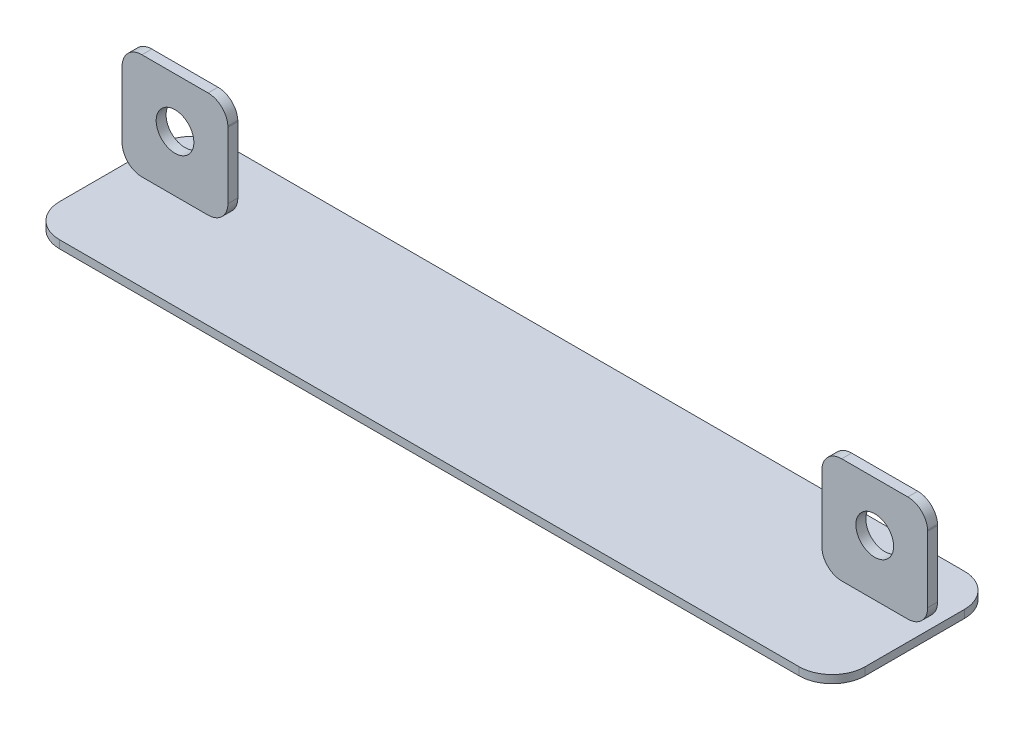
SolidWorks part; units mm, degrees
ref_plane "Front Plane" through (0, 0, 0) normal (0, 0, 1) x (1, 0, 0)
ref_plane "Top Plane" through (0, 0, 0) normal (0, 1, 0) x (1, 0, 0)
ref_plane "Right Plane" through (0, 0, 0) normal (1, 0, 0) x (0, 0, -1)
sketch "Sketch3" plane through (0, 0, 0) normal (0, 0, 1) x (1, 0, 0)
  line L6 (-7.9975, -43.2281) -> (-8, -43.4)
  line L7 (-8, -43.4) -> (-8, -53.4)
  line L8 (-5, -56.4) -> (5, -56.4)
  line L9 (8, -53.4) -> (8, -43.4)
  line L10 (8, -43.4) -> (7.9975, -43.2281)
  line L11 (5, -40.4) -> (-5, -40.4)
  line L12 (-7.9975, -43.2281) -> (-8, -43.4)
  line L13 (-8, -43.4) -> (-8, -53.4)
  line L14 (-5, -56.4) -> (5, -56.4)
  line L15 (8, -53.4) -> (8, -43.4)
  line L16 (8, -43.4) -> (7.9975, -43.2281)
  line L17 (5, -40.4) -> (-5, -40.4)
  line L18 (110.8, -40.4) -> (100.8, -40.4)
  line L19 (97.8025, -43.2281) -> (97.8, -43.4)
  line L20 (97.8, -43.4) -> (97.8, -53.4)
  line L21 (100.8, -56.4) -> (110.8, -56.4)
  line L22 (113.8, -53.4) -> (113.8, -43.4)
  line L23 (113.8, -43.4) -> (113.7975, -43.2281)
  line L24 (110.8, -40.4) -> (100.8, -40.4)
  line L25 (97.8025, -43.2281) -> (97.8, -43.4)
  line L26 (97.8, -43.4) -> (97.8, -53.4)
  line L27 (100.8, -56.4) -> (110.8, -56.4)
  line L28 (113.8, -53.4) -> (113.8, -43.4)
  line L29 (113.8, -43.4) -> (113.7975, -43.2281)
  circle A0 centre (0, -47.9524) radius 2.85 construction
  circle A1 centre (0, -47.9524) radius 2.85
  arc A2 (-5, -40.4) -> (-7.9975, -43.2281) centre (-5.0013, -43.4012) ccw
  arc A3 (-8, -53.4) -> (-5, -56.4) centre (-5, -53.4) ccw
  arc A4 (5, -56.4) -> (8, -53.4) centre (5, -53.4) ccw
  arc A5 (7.9975, -43.2281) -> (5, -40.4) centre (5.0013, -43.4012) ccw
  arc A6 (-5, -40.4) -> (-7.9975, -43.2281) centre (-5.0013, -43.4012) ccw
  arc A7 (-8, -53.4) -> (-5, -56.4) centre (-5, -53.4) ccw
  arc A8 (5, -56.4) -> (8, -53.4) centre (5, -53.4) ccw
  arc A9 (7.9975, -43.2281) -> (5, -40.4) centre (5.0013, -43.4012) ccw
  circle A10 centre (105.8, -47.9524) radius 2.85 construction
  circle A11 centre (105.8, -47.9524) radius 2.85
  arc A12 (100.8, -40.4) -> (97.8025, -43.2281) centre (100.7987, -43.4012) ccw
  arc A13 (97.8, -53.4) -> (100.8, -56.4) centre (100.8, -53.4) ccw
  arc A14 (110.8, -56.4) -> (113.8, -53.4) centre (110.8, -53.4) ccw
  arc A15 (113.7975, -43.2281) -> (110.8, -40.4) centre (110.8013, -43.4012) ccw
  arc A16 (100.8, -40.4) -> (97.8025, -43.2281) centre (100.7987, -43.4012) ccw
  arc A17 (97.8, -53.4) -> (100.8, -56.4) centre (100.8, -53.4) ccw
  arc A18 (110.8, -56.4) -> (113.8, -53.4) centre (110.8, -53.4) ccw
  arc A19 (113.7975, -43.2281) -> (110.8, -40.4) centre (110.8013, -43.4012) ccw
  dimension "D1" = 0
  dimension "D2" = 0
extrude "Boss-Extrude3" add sketch "Sketch3" along normal up to surface (1.5 mm away)
sketch "Sketch2" plane through (0, -56.4, 0) normal (0, -1, 0) x (1, 0, 0)
  line L0 (-8, -78.8637) -> (-8, 0) construction
  line L1 (-8, -9.0521) -> (113.8, -9.0521)
  line L2 (-8, -9.0521) -> (-8, 15.9479)
  line L3 (-8, 15.9479) -> (113.8, 15.9479)
  line L4 (113.8, -9.0521) -> (113.8, 15.9479)
  line L5 (113.8, 0) -> (113.8, -78.8637) construction
  line L6 (-5, 15.9479) -> (5, 15.9479) construction
  dimension "D1" = 25
extrude "Boss-Extrude2" add sketch "Sketch2" along normal blind 1.2
fillet "Fillet1" radius 5 4 edges at (113.8, -57, 15.9479) (113.8, -57, -9.0521) (-8, -57, -9.0521) (-8, -57, 15.9479)
